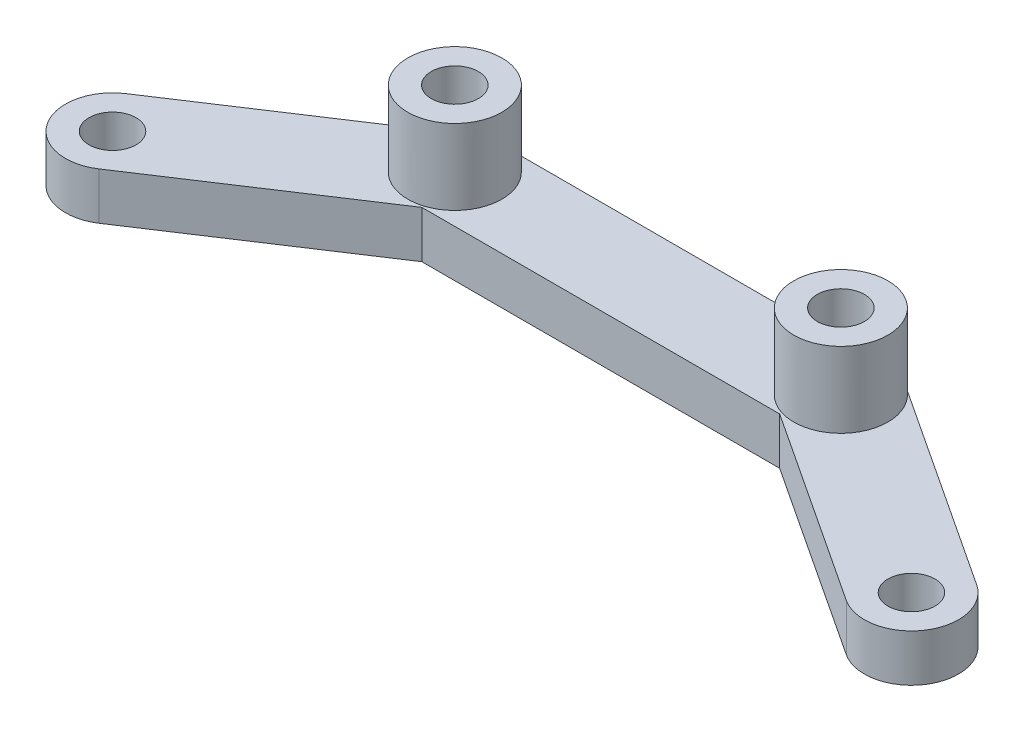
SolidWorks part; units mm, degrees
ref_plane "Front Plane" through (0, 0, 0) normal (0, 0, 1) x (1, 0, 0)
ref_plane "Top Plane" through (0, 0, 0) normal (0, 1, 0) x (1, 0, 0)
ref_plane "Right Plane" through (0, 0, 0) normal (1, 0, 0) x (0, 0, -1)
sketch "Sketch1" plane through (0, 0, 0) normal (0, 1, 0) x (1, 0, 0)
  line L1 (-42.4264, 42.4264) -> (42.4264, 42.4264)
  line L2 (-42.4264, 42.4264) -> (-42.4264, -42.4264)
  line L3 (-42.4264, -42.4264) -> (42.4264, -42.4264)
  line L4 (42.4264, 42.4264) -> (42.4264, -42.4264)
  line L5 (-42.4264, 42.4264) -> (42.4264, -42.4264) construction
  line L6 (-42.4264, -42.4264) -> (42.4264, 42.4264) construction
  line L7 (-20.5, 28) -> (20.5, 28)
  line L8 (-20.5, 28) -> (-20.5, -28)
  line L9 (-20.5, -28) -> (20.5, -28)
  line L10 (20.5, 28) -> (20.5, -28)
  line L11 (-20.5, 28) -> (20.5, -28) construction
  line L12 (-20.5, -28) -> (20.5, 28) construction
  point P0 (0, 0)
  point P6 (0, 0)
  dimension "D1" = 120
  dimension "D2" = 41
  dimension "D3" = 56
sketch "Sketch2" plane through (0, 0, 0) normal (0, 1, 0) x (1, 0, 0)
  line L0 (-42.4264, -42.4264) -> (-20.5, -28) construction
  line L1 (-20.5, -28) -> (20.5, -28) construction
  line L2 (20.5, -28) -> (42.4264, -42.4264) construction
  line L3 (-39.6782, -46.6034) -> (-19.0026, -33)
  line L4 (-19.0026, -33) -> (19.0026, -33)
  line L5 (19.0026, -33) -> (39.6782, -46.6034)
  line L6 (-45.1746, -38.2494) -> (-21.9974, -23)
  line L7 (-21.9974, -23) -> (21.9974, -23)
  line L8 (21.9974, -23) -> (45.1746, -38.2494)
  circle A0 centre (-42.4264, -42.4264) radius 2.5
  circle A1 centre (-20.5, -28) radius 2.5
  circle A2 centre (20.5, -28) radius 2.5
  circle A3 centre (42.4264, -42.4264) radius 2.5
  arc A4 (-39.6782, -46.6034) -> (-45.1746, -38.2494) centre (-42.4264, -42.4264) cw
  arc A5 (39.6782, -46.6034) -> (45.1746, -38.2494) centre (42.4264, -42.4264) ccw
  dimension "D1" = 5
  dimension "D2" = 5
  dimension "D3" = 5
extrude "Boss-Extrude1" add sketch "Sketch2" along normal blind 5
sketch "Sketch3" plane through (0, 5, 0) normal (0, 1, 0) x (1, 0, 0)
  line L0 (21.9974, -23) -> (-21.9974, -23) construction
  circle A0 centre (-20.5, -28) radius 5
  circle A1 centre (20.5, -28) radius 5
  circle A2 centre (20.5, -28) radius 2.5 construction
  circle A3 centre (-20.5, -28) radius 2.5
  circle A4 centre (20.5, -28) radius 2.5
  circle A5 centre (-20.5, -28) radius 2.5 construction
extrude "Boss-Extrude2" add sketch "Sketch3" along normal blind 8
fillet "Fillet1" radius 5 2 edges at (21.9974, 2.5, 23) (-21.9974, 2.5, 23)
